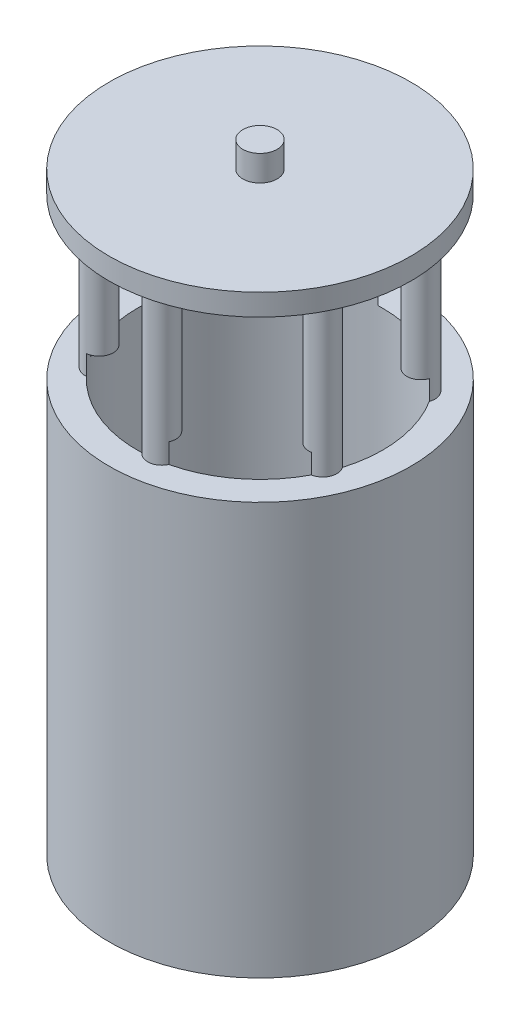
SolidWorks part; units mm, degrees
ref_plane "Front Plane" through (0, 0, 0) normal (0, 0, 1) x (1, 0, 0)
ref_plane "Top Plane" through (0, 0, 0) normal (0, 1, 0) x (1, 0, 0)
ref_plane "Right Plane" through (0, 0, 0) normal (1, 0, 0) x (0, 0, -1)
sketch "Sketch1" plane through (0, 0, 0) normal (0, 1, 0) x (1, 0, 0)
  circle A0 centre (0, 0) radius 27.955
  dimension "D1" = 55.91
extrude "Boss-Extrude1" add sketch "Sketch1" along normal blind 4
sketch "Sketch2" plane through (0, 4, 0) normal (0, 1, 0) x (1, 0, 0)
  circle A0 centre (0, 0) radius 3.175
  dimension "D1" = 6.35
extrude "Boss-Extrude2" add sketch "Sketch2" along normal blind 4.76
sketch "Sketch3" plane through (0, 0, 0) normal (0, -1, 0) x (1, 0, 0)
  circle A0 centre (0, 0) radius 21.2558
  circle A1 centre (2.874, 21.0606) radius 2.6153
  circle A2 centre (19.6761, 8.0413) radius 2.6153
  circle A3 centre (16.802, -13.0193) radius 2.6153
  circle A4 centre (-2.874, -21.0606) radius 2.6153
  circle A5 centre (-19.6761, -8.0413) radius 2.6153
  circle A6 centre (-16.802, 13.0193) radius 2.6153
  point P17 (0, 0)
  dimension "D1" = 6
extrude "Boss-Extrude3" add sketch "Sketch3" along normal blind 29.718 contours A0 A4 | A0 A4 | A0 A3 | A0 A3 | A0 A2 | A0 A2 | A0 A1 | A0 A1 | A0 A6 | A0 A6 | A0 A5 | A0 A5 region at (18.6222, 0, 7.6106) region at (20.6763, 0, 8.4501) region at (17.6561, 0, -13.6811) region at (15.9021, 0, -12.322) region at (2.7201, 0, 19.9327) region at (3.0201, 0, 22.1312) region at (-3.0201, 0, -22.1312) region at (-2.7201, 0, -19.9327) region at (-15.9021, 0, 12.322) region at (-17.6561, 0, 13.6811) region at (-20.6763, 0, -8.4501) region at (-18.6222, 0, -7.6106)
sketch "Sketch4" plane through (0, -29.718, 0) normal (0, -1, 0) x (1, 0, 0)
  circle A0 centre (0, 0) radius 27.955
extrude "Boss-Extrude4" add sketch "Sketch4" along normal blind 76.35
sketch "Sketch5" plane through (0, -106.068, 0) normal (0, -1, 0) x (1, 0, 0)
  circle A0 centre (0, 0) radius 22.7587
extrude "Cut-Extrude1" cut sketch "Sketch5" against normal blind 80
